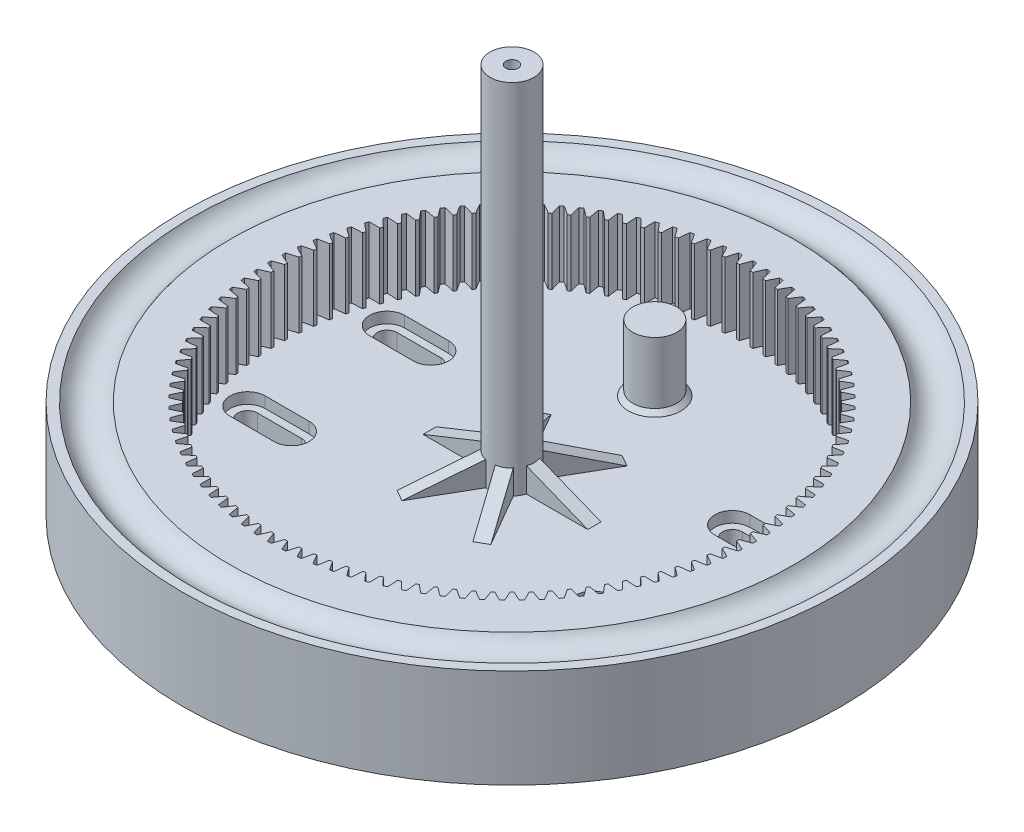
SolidWorks part; units mm, degrees
ref_plane "Front Plane" through (0, 0, 0) normal (0, 0, 1) x (1, 0, 0)
ref_plane "Top Plane" through (0, 0, 0) normal (0, 1, 0) x (1, 0, 0)
ref_plane "Right Plane" through (0, 0, 0) normal (1, 0, 0) x (0, 0, -1)
sketch "Sketch1" plane through (0, 0, 0) normal (0, 1, 0) x (1, 0, 0)
  circle A0 centre (0, 0) radius 75
  dimension "D1" = 150
extrude "Boss-Extrude1" add sketch "Sketch1" along normal blind 22.5
sketch "Sketch2" plane through (0, 0, 0) normal (0, 0, 1) x (1, 0, 0)
  line L0 (-68.5, 8.6344) -> (-68.5, 36.3656) construction
  line L1 (-72.8301, 22.5) -> (-64.1699, 22.5)
  line L8 (0, 0) -> (0, 80) construction
  line L11 (-75, 22.5) -> (-75, 0) construction
  line L12 (75, 22.5) -> (-75, 22.5) construction
  arc A0 (-64.1699, 22.5) -> (-72.8301, 22.5) centre (-68.5, 25) cw
  point P3 (-68.5, 22.5)
  dimension "D2" = 5
  dimension "D1" = 6.5
  dimension "D3" = 2.5
revolve "Cut-Revolve1" cut sketch "Sketch2" angle 360 about L8 region at (-68.5, 21.4749, 0)
sketch "Sketch3" plane through (0, 22.5, 0) normal (0, 1, 0) x (1, 0, 0)
  circle A0 centre (0, 0) radius 58
  dimension "D1" = 116
extrude "Cut-Extrude1" cut sketch "Sketch3" against normal blind 15
sketch "Sketch5" plane through (0, 22.5, 0) normal (0, 1, 0) x (1, 0, 0)
  arc A0 (-2.8138, 55.1793) -> (-0.3994, 55.2496) centre (0, 0) cw
  arc A6 (-0.3994, 55.2496) -> (-1.2151, 52.9861) centre (24.5686, 44.9735) ccw
  arc A8 (-1.2151, 52.9861) -> (-1.8679, 52.9671) centre (0, 0) ccw
  arc A9 (-1.8679, 52.9671) -> (-2.8138, 55.1793) centre (-27.1421, 43.4689) ccw
sketch "Sketch4" plane through (0, 22.5, 0) normal (0, 1, 0) x (1, 0, 0)
  circle A0 centre (0, 0) radius 55.251
  circle A3 centre (0, 0) radius 58
  circle A4 centre (0, 0) radius 58 construction
extrude "Boss-Extrude2" add sketch "Sketch4" against normal up to surface (15 mm away) up to face at (0, 7.5, 58)
extrude "Boss-Extrude3" add sketch "Sketch5" against normal up to surface (15 mm away) up to face at (0, 7.5, 55.251)
pattern_circular "CirPattern1" count 108 over 360 about axis through (0, 22.5, 0) along (0, 1, 0) of "Boss-Extrude3"
sketch "Sketch6" plane through (0, 7.5, 0) normal (0, 1, 0) x (1, 0, 0)
  circle A0 centre (0, 0) radius 5
  dimension "D1" = 10
extrude "Boss-Extrude4" add sketch "Sketch6" along normal blind 81.5
sketch "Sketch7" plane through (0, 89, 0) normal (0, 1, 0) x (1, 0, 0)
  circle A0 centre (0, 0) radius 1.4
  dimension "D1" = 2.8
extrude "Cut-Extrude2" cut sketch "Sketch7" against normal blind 10
sketch "Sketch8" plane through (0, 0, 0) normal (0, 0, 1) x (1, 0, 0)
  line L0 (0, 15) -> (-25, 5)
  line L2 (0, 15) -> (0, 5)
  line L4 (0, 5) -> (-25, 5)
  line L6 (0, 0) -> (0, 29.2809) construction
  dimension "D1" = 25
  dimension "D2" = 10
extrude "Boss-Extrude5" add sketch "Sketch8" along normal blind 1.5 and the other way blind 1.5
pattern_circular "CirPattern2" count 6 over 360 about axis through (0, 89, 0) along (0, -1, 0) of "Boss-Extrude5"
sketch "Sketch9" plane through (0, 0, 0) normal (0, -1, 0) x (1, 0, 0)
  line L0 (0, 75) -> (0, -75) construction
  line L1 (75, 0) -> (-75, 0) construction
  line L2 (-44.3, 15.875) -> (-34.3, 15.875) construction
  line L3 (-44.3, 18.125) -> (-34.3, 18.125)
  line L4 (-44.3, 13.625) -> (-34.3, 13.625)
  line L5 (44.3, 15.875) -> (34.3, 15.875) construction
  line L6 (44.3, 18.125) -> (34.3, 18.125)
  line L7 (44.3, 13.625) -> (34.3, 13.625)
  line L8 (44.3, -15.875) -> (34.3, -15.875) construction
  line L9 (44.3, -18.125) -> (34.3, -18.125)
  line L10 (44.3, -13.625) -> (34.3, -13.625)
  line L11 (-44.3, -15.875) -> (-34.3, -15.875) construction
  line L12 (-44.3, -18.125) -> (-34.3, -18.125)
  line L13 (-44.3, -13.625) -> (-34.3, -13.625)
  circle A0 centre (0, 0) radius 75 construction
  arc A1 (-44.3, 18.125) -> (-44.3, 13.625) centre (-44.3, 15.875) ccw
  arc A2 (-34.3, 13.625) -> (-34.3, 18.125) centre (-34.3, 15.875) ccw
  arc A3 (44.3, 18.125) -> (44.3, 13.625) centre (44.3, 15.875) cw
  arc A4 (34.3, 13.625) -> (34.3, 18.125) centre (34.3, 15.875) cw
  arc A5 (44.3, -18.125) -> (44.3, -13.625) centre (44.3, -15.875) ccw
  arc A6 (34.3, -13.625) -> (34.3, -18.125) centre (34.3, -15.875) ccw
  arc A7 (-44.3, -18.125) -> (-44.3, -13.625) centre (-44.3, -15.875) cw
  arc A8 (-34.3, -13.625) -> (-34.3, -18.125) centre (-34.3, -15.875) cw
  point P9 (-39.3, 15.875)
  point P16 (39.3, 15.875)
  point P23 (39.3, -15.875)
  point P30 (-39.3, -15.875)
  point P38 (0, 8.125)
  dimension "D1" = 4.5
  dimension "D2" = 10
  dimension "D3" = 39.3
  dimension "D4" = 15.875
extrude "Cut-Extrude3" cut sketch "Sketch9" against normal up to surface (7.5 mm away) up to face at (0, 7.5, 0)
sketch "Sketch10" plane through (0, 7.5, 0) normal (0, 1, 0) x (1, 0, 0)
  line L0 (0, 64.1699) -> (0, -64.1699) construction
  line L1 (64.1699, 0) -> (-64.1699, 0) construction
  line L2 (-39.3, 18.125) -> (-39.3, 13.625) construction
  line L3 (-44.3, 18.125) -> (-34.3, 18.125) construction
  line L4 (-34.3, 13.625) -> (-44.3, 13.625) construction
  line L5 (-44.3, 15.875) -> (-34.3, 15.875) construction
  line L6 (-44.3, 19.875) -> (-34.3, 19.875)
  line L7 (-44.3, 11.875) -> (-34.3, 11.875)
  line L8 (44.3, 15.875) -> (34.3, 15.875) construction
  line L9 (44.3, 19.875) -> (34.3, 19.875)
  line L10 (44.3, 11.875) -> (34.3, 11.875)
  line L11 (44.3, -15.875) -> (34.3, -15.875) construction
  line L12 (44.3, -19.875) -> (34.3, -19.875)
  line L13 (44.3, -11.875) -> (34.3, -11.875)
  line L14 (-44.3, -15.875) -> (-34.3, -15.875) construction
  line L15 (-44.3, -19.875) -> (-34.3, -19.875)
  line L16 (-44.3, -11.875) -> (-34.3, -11.875)
  circle A0 centre (0, 0) radius 64.1699 construction
  arc A1 (-44.3, 19.875) -> (-44.3, 11.875) centre (-44.3, 15.875) ccw
  arc A2 (-34.3, 11.875) -> (-34.3, 19.875) centre (-34.3, 15.875) ccw
  arc A3 (44.3, 19.875) -> (44.3, 11.875) centre (44.3, 15.875) cw
  arc A4 (34.3, 11.875) -> (34.3, 19.875) centre (34.3, 15.875) cw
  arc A5 (44.3, -19.875) -> (44.3, -11.875) centre (44.3, -15.875) ccw
  arc A6 (34.3, -11.875) -> (34.3, -19.875) centre (34.3, -15.875) ccw
  arc A7 (-44.3, -19.875) -> (-44.3, -11.875) centre (-44.3, -15.875) cw
  arc A8 (-34.3, -11.875) -> (-34.3, -19.875) centre (-34.3, -15.875) cw
  point P15 (-39.3, 15.875)
  point P22 (39.3, 15.875)
  point P29 (39.3, -15.875)
  point P36 (-39.3, -15.875)
  point P44 (0, 8.125)
  dimension "D1" = 8
  dimension "D2" = 10
extrude "Cut-Extrude4" cut sketch "Sketch10" against normal blind 2.5
sketch "Sketch11" plane through (0, 7.5, 0) normal (0, 1, 0) x (1, 0, 0)
  circle A0 centre (0, 0) radius 32.5 construction
  circle A1 centre (0, 32.5) radius 5
  dimension "D1" = 65
  dimension "D2" = 10
extrude "Boss-Extrude6" add sketch "Sketch11" along normal up to surface (15 mm away) up to face at (0, 22.5, -64.1699)
chamfer "Chamfer1" distance 1 angle 45 1 edges at (0, 7.5, -27.5)
